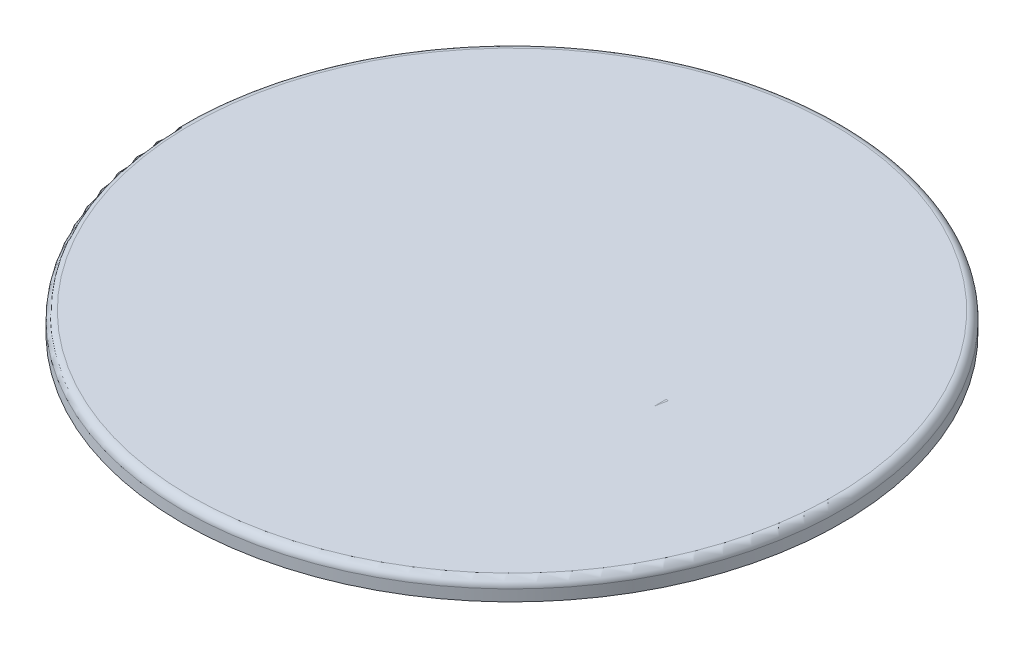
SolidWorks part; units mm, degrees
material "1060 Alloy"
ref_plane "Front Plane" through (0, 0, 0) normal (0, 0, 1) x (1, 0, 0)
ref_plane "Top Plane" through (0, 0, 0) normal (0, 1, 0) x (1, 0, 0)
ref_plane "Right Plane" through (0, 0, 0) normal (1, 0, 0) x (0, 0, -1)
sketch "Sketch1" plane through (0, 0, 0) normal (0, 1, 0) x (1, 0, 0)
  circle A0 centre (0, 0) radius 19.4
  dimension "D1" = 38.8
extrude "Boss-Extrude1" add sketch "Sketch1" along normal blind 15
sketch "Sketch2" plane through (0, 15, 0) normal (0, 1, 0) x (1, 0, 0)
  circle A0 centre (0, 0) radius 41
  dimension "D1" = 82
extrude "Boss-Extrude2" add sketch "Sketch2" along normal blind 2.4
fillet "Fillet1" radius 2 1 edges at (0, 15, 19.4)
fillet "Fillet3" radius 2 1 edges at (0, 0, 19.4)
fillet "Fillet5" radius 1 1 edges at (0, 17.4, 41)
sketch "Sketch3" plane through (0, 0, 0) normal (0, 0, 1) x (1, 0, 0)
  line L0 (19.4, 15.2) -> (19.4, 17.2) construction
  line L1 (19.4, 2) -> (19.4, 13) construction
  line L2 (-17.4, 0) -> (17.4, 0) construction
  line L3 (19.4, 16.2) -> (21.6, 16.2) construction
  line L4 (21.6, 16.7) -> (21.6, 15.7) construction
  line L5 (19.4, 15.2) -> (21.6, 15.7) construction
  line L6 (19.4, 17.2) -> (21.6, 16.7) construction
  line L7 (19.2, 17.4506) -> (21.8, 16.8596)
  line L8 (21.8, 16.8596) -> (21.8, 15.5404)
  line L9 (19.2, 14.9494) -> (21.8, 15.5404)
  line L10 (19.2, 14.9494) -> (19.2, 17.4506)
  dimension "D1" = 15.2
  dimension "D2" = 2
  dimension "D3" = 2.2
  dimension "D4" = 0.5
  dimension "D5" = 0.2
ref_plane "Plane1" through (0, 16.2, 0) normal (0, -1, 0) x (-1, 0, 0)
sketch "Sketch4" plane through (0, 16.2, 0) normal (0, -1, 0) x (-1, 0, 0)
  circle A0 centre (0, 0) radius 19.4
  dimension "D1" = 38.8
curve "Helix/Spiral1" pitch 4.3333 height 15.1667 radius 19.4 centre (0, 16.2, 0) axis (0, -1, 0) start towards (1, 0, 0)
sweep "Sweep1" add profiles "Sketch3" path "Helix/Spiral1"
chamfer "Chamfer3" [suppressed] distance 11 angle 10
chamfer "Chamfer4" [suppressed] distance 1 angle 45
fillet "Fillet6" [suppressed] radius 1
fillet "Fillet7" [suppressed] radius 0.2
